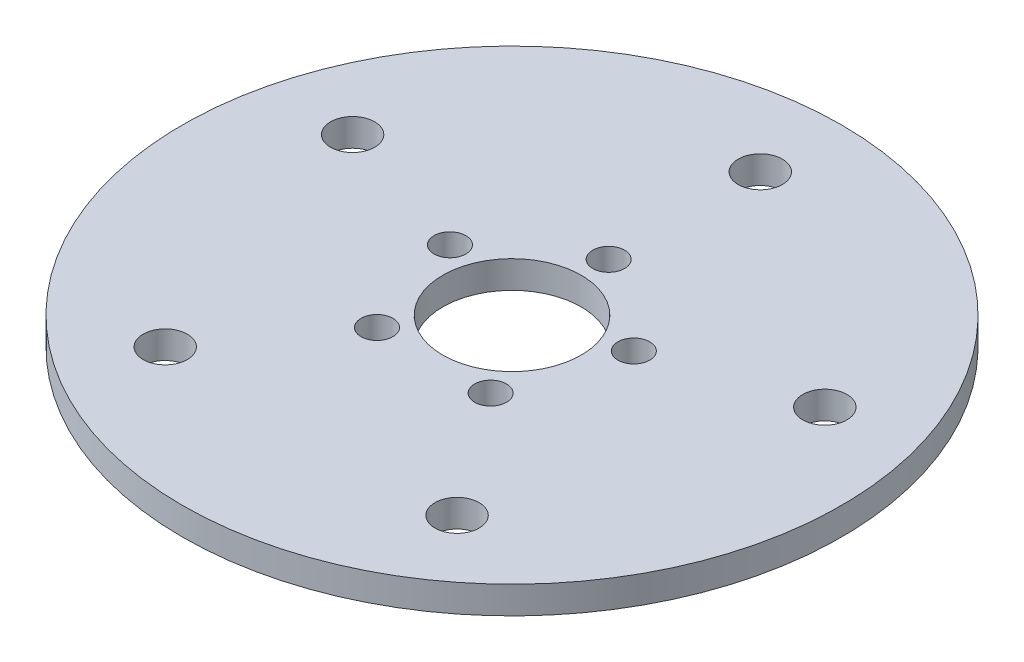
SolidWorks part; units mm, degrees
material "6061 Alloy"
ref_plane "Front Plane" through (0, 0, 0) normal (0, 0, 1) x (1, 0, 0)
ref_plane "Top Plane" through (0, 0, 0) normal (0, 1, 0) x (1, 0, 0)
ref_plane "Right Plane" through (0, 0, 0) normal (1, 0, 0) x (0, 0, -1)
sketch "Sketch1" plane through (0, 807.1164, 0) normal (0, 1, 0) x (-1, 0, 0)
  circle A0 centre (0, 0) radius 38.1
  point P2 (0, 0)
  point P5 (1.3649, -632.9221)
  point P13 (0, 0)
  point P23 (-1.8225, -621.617)
  dimension "D1" = 76.2
extrude "Boss-Extrude1" add sketch "Sketch1" against normal blind 3.175
sketch "Sketch2" plane through (0, 807.1164, 0) normal (0, 1, 0) x (1, 0, 0)
  line L0 (0, 0) -> (0, 11.176) construction
  line L1 (0, 0) -> (0, 28.702) construction
  circle A0 centre (0, 0) radius 8.001
  circle A1 centre (0, 0) radius 38.1 construction
  circle A2 centre (0, 11.176) radius 1.8415
  circle A3 centre (10.629, 3.4536) radius 1.8415
  circle A4 centre (6.5691, -9.0416) radius 1.8415
  circle A5 centre (-6.5691, -9.0416) radius 1.8415
  circle A6 centre (-10.629, 3.4536) radius 1.8415
  circle A7 centre (0, 28.702) radius 2.5527
  circle A8 centre (27.2972, 8.8694) radius 2.5527
  circle A9 centre (16.8706, -23.2204) radius 2.5527
  circle A10 centre (-16.8706, -23.2204) radius 2.5527
  circle A11 centre (-27.2972, 8.8694) radius 2.5527
  point P18 (-24.1969, 14.2419)
  point P19 (0, 0)
  point P27 (0, 0)
  dimension "D1" = 16.002
  dimension "D2" = 3.683
  dimension "D6" = 5.1054
  dimension "D3" = 11.176
  dimension "D5" = 28.702
  dimension "D4" = 5
  dimension "D7" = 5
extrude "Cut-Extrude1" cut sketch "Sketch2" against normal through all
